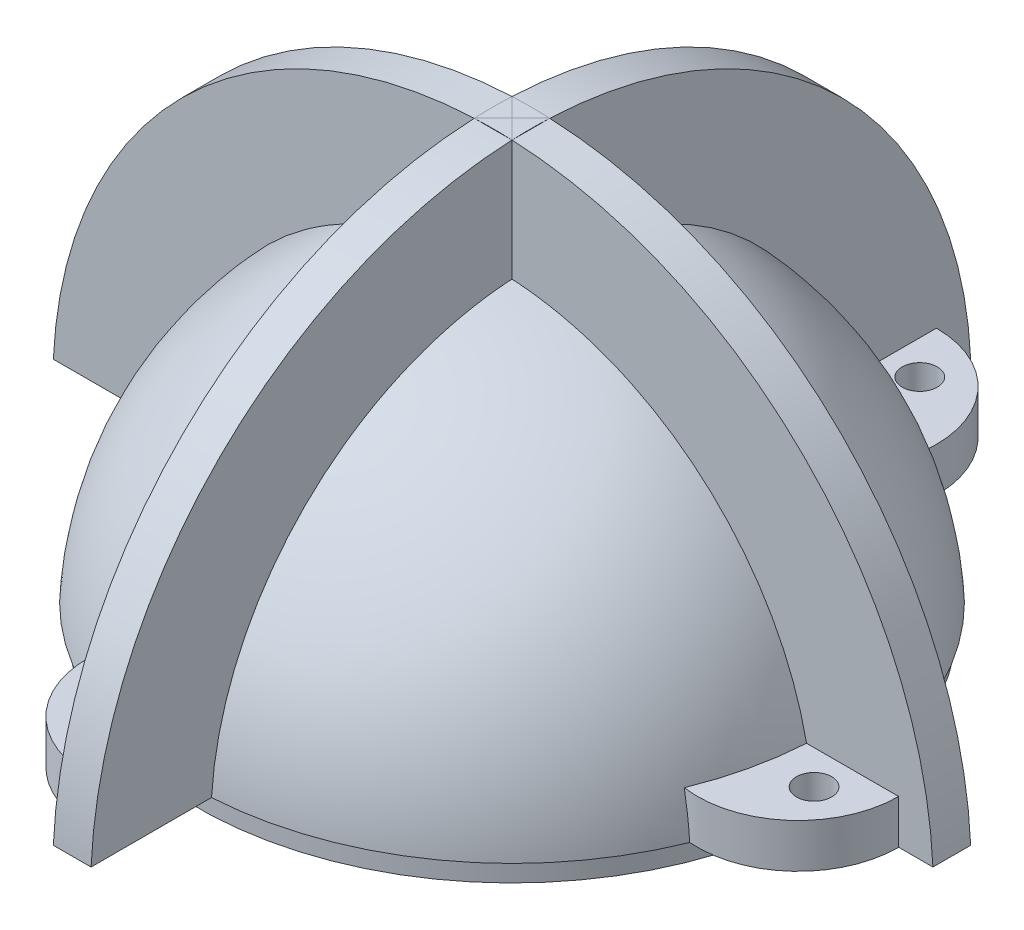
SolidWorks part; units mm, degrees
ref_plane "Front Plane" through (0, 0, 0) normal (0, 0, 1) x (1, 0, 0)
ref_plane "Top Plane" through (0, 0, 0) normal (0, 1, 0) x (1, 0, 0)
ref_plane "Right Plane" through (0, 0, 0) normal (1, 0, 0) x (0, 0, -1)
sketch "Sketch1" plane through (0, 0, 0) normal (0, 0, 1) x (1, 0, 0)
  line L0 (-25.485, 0) -> (-24.285, 0)
  line L1 (-24.285, 0) -> (-22.085, 0)
  line L2 (-24.285, 0) -> (-24.285, 0.5)
  line L3 (-24.285, 0.5) -> (-22.085, 0.5)
  line L4 (-22.085, 0) -> (-22.085, 0.5)
  line L5 (-22.085, 0) -> (-20.885, 0)
  line L6 (-20.885, 0) -> (-20.885, 11.7939)
  line L7 (0, 25.485) -> (0, 23.985)
  line L8 (0, 0) -> (0, 23.985) construction
  arc A0 (-25.485, 0) -> (0, 25.485) centre (0, 0) cw
  arc A1 (-20.885, 11.7939) -> (0, 23.985) centre (0, 0) cw
  dimension "D1" = 1.2
  dimension "D2" = 1.5
  dimension "D3" = 0.5
  dimension "D4" = 2.2
  dimension "D5" = 22.085
revolve "Revolve1" add sketch "Sketch1" angle 360 about L8 region at (-17.7658, 17.7658, 0)
sketch "Sketch2" plane through (0, 0, 0) normal (0, 0, 1) x (1, 0, 0)
  line L0 (-25.485, 0) -> (25.485, 0) construction
  line L1 (-24.9, 0) -> (-35, 0)
  line L3 (35, 0) -> (24.9, 0)
  arc A0 (-35, 0) -> (35, 0) centre (0, 0) cw
  arc A1 (-24.9, 0) -> (24.9, 0) centre (0, 0) cw
  dimension "D1" = 24.9
  dimension "D2" = 35
extrude "Boss-Extrude1" add sketch "Sketch2" along normal blind 1.5 and the other way blind 1.5 separate body
sketch "Sketch3" plane through (0, 0, 0) normal (1, 0, 0) x (0, 0, -1)
  line L0 (35, 0) -> (24.9, 0)
  line L1 (-24.9, 0) -> (-35, 0)
  line L2 (-25.485, 0) -> (25.485, 0) construction
  arc A0 (24.9, 0) -> (-24.9, 0) centre (0, 0) ccw
  arc A2 (35, 0) -> (-35, 0) centre (0, 0) ccw
  dimension "D1" = 35
  dimension "D2" = 24.9
extrude "Boss-Extrude2" add sketch "Sketch3" along normal blind 1.5 and the other way blind 1.5
sketch "Sketch4" plane through (0, 0, 0) normal (0, 0, 1) x (1, 0, 0)
  line L0 (-35, 0) -> (-24.9, 0) construction
  line L1 (-24.8453, 0) -> (-35.8975, 0)
  line L2 (-35.8975, 0) -> (-35.8975, 1.65)
  line L3 (-35.8975, 1.65) -> (-24.8453, 1.65)
  line L4 (0, 0) -> (0, 6.0763) construction
  line L5 (-24.8453, 1.65) -> (-24.8453, 0)
  line L6 (-25.485, 0) -> (25.485, 0) construction
  arc A2 (-1.5, 24.8548) -> (-24.9, 0) centre (0, 0) ccw construction
  dimension "D2" = 1.65
revolve "Cut-Revolve2" cut sketch "Sketch4" angle 360 about L4 region at (-30.3714, 0.825, 0)
sketch "Sketch5" plane through (0, 1.65, 0) normal (0, -1, 0) x (1, 0, 0)
  line L1 (-34.9611, -1.5) -> (-24.8453, -1.5) construction
  line L26 (-32.2386, -1.5) -> (-24.2386, -1.5)
  line L43 (24.2386, 1.5) -> (32.2386, 1.5)
  line L44 (-1.5, 32.2386) -> (-1.5, 24.2386)
  line L45 (1.5, -32.2386) -> (1.5, -24.2386)
  circle A4 centre (-28.2128, -4.2) radius 1.4
  arc A23 (-30.6955, -6.2233) -> (-32.2386, -1.5) centre (-24.2386, -1.5) cw
  circle A25 centre (0, 0) radius 24.285 construction
  arc A26 (-30.6955, -6.2233) -> (-22.4361, -9.2943) centre (-24.2386, -1.5) ccw
  circle A27 centre (0, 0) radius 24.285 construction
  arc A28 (-22.4361, -9.2943) -> (-24.2386, -1.5) centre (0, 0) cw
  arc A29 (-9.2943, 22.4361) -> (-1.5, 24.2386) centre (0, 0) cw
  arc A30 (-6.2233, 30.6955) -> (-1.5, 32.2386) centre (-1.5, 24.2386) cw
  arc A31 (-6.2233, 30.6955) -> (-9.2943, 22.4361) centre (-1.5, 24.2386) ccw
  circle A32 centre (-4.2, 28.2128) radius 1.4
  arc A33 (22.4361, 9.2943) -> (24.2386, 1.5) centre (0, 0) cw
  arc A34 (30.6955, 6.2233) -> (32.2386, 1.5) centre (24.2386, 1.5) cw
  arc A35 (30.6955, 6.2233) -> (22.4361, 9.2943) centre (24.2386, 1.5) ccw
  circle A36 centre (28.2128, 4.2) radius 1.4
  arc A37 (9.2943, -22.4361) -> (1.5, -24.2386) centre (0, 0) cw
  arc A38 (6.2233, -30.6955) -> (1.5, -32.2386) centre (1.5, -24.2386) cw
  arc A39 (6.2233, -30.6955) -> (9.2943, -22.4361) centre (1.5, -24.2386) ccw
  circle A40 centre (4.2, -28.2128) radius 1.4
  dimension "D2" = 2.8
  dimension "D5" = 8
  dimension "D1" = 4
  dimension "D3" = 28.5237
  dimension "D4" = 2.7
extrude "Boss-Extrude20" add sketch "Sketch5" against normal blind 3.5
sketch "Sketch6" plane through (0, 0, 0) normal (0, -1, 0) x (1, 0, 0)
  circle A0 centre (0, 0) radius 25
  circle A1 centre (0, 0) radius 26
  dimension "D1" = 50
  dimension "D2" = 52
extrude "Cut-Extrude1" cut sketch "Sketch6" against normal up to surface (1.65 mm away) up to face at (-28.2128, 1.65, -5.6)
ref_plane "Plane1" through (0, 0, 0) normal (0.7071, 0, -0.7071) x (-0.7071, 0, -0.7071)
